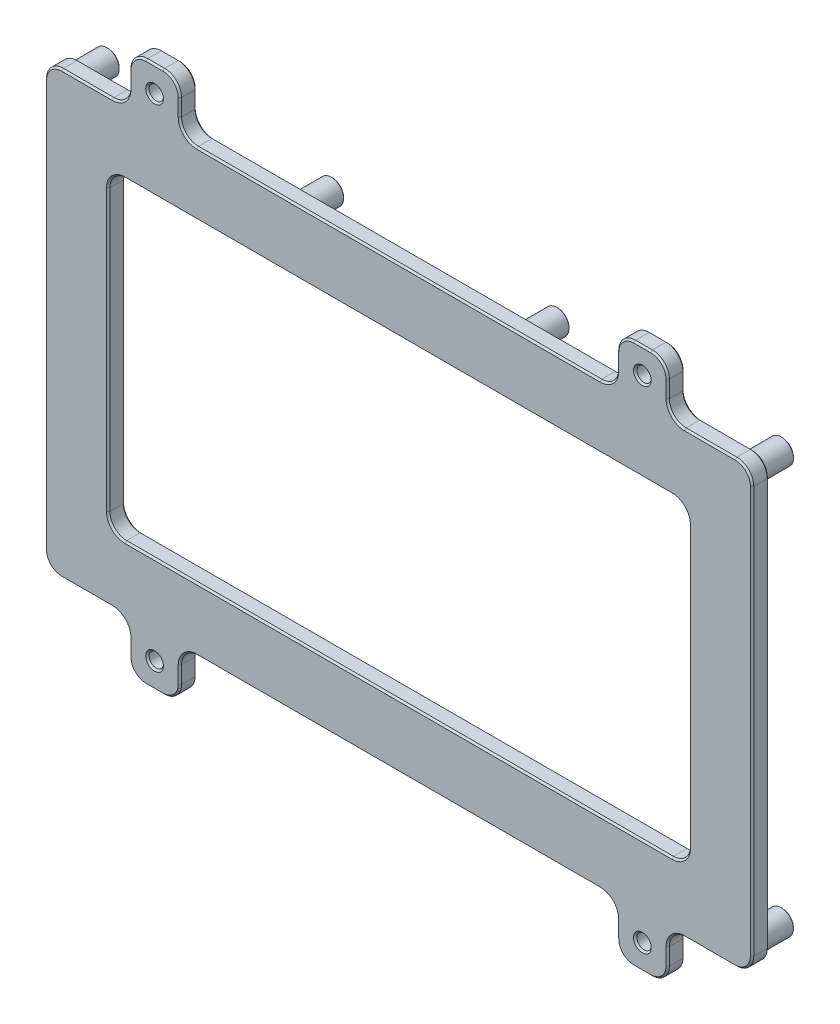
SolidWorks part; units mm, degrees
note: The reader was unsure of these and kept them because the rebuilt part matched: shared geometry of "Sketch1<5>".
ref_plane "Front Plane" through (0, 0, 0) normal (0, 0, 1) x (1, 0, 0)
ref_plane "Top Plane" through (0, 0, 0) normal (0, 1, 0) x (1, 0, 0)
ref_plane "Right Plane" through (0, 0, 0) normal (1, 0, 0) x (0, 0, -1)
sketch "Sketch1" plane through (0, 0, 0) normal (0, 0, 1) x (1, 0, 0)
  line L0 (71.9383, -41.7764) -> (71.9383, -44.6889) construction
  line L1 (-91.7492, -45.6889) -> (75.8508, -45.6889)
  line L2 (-91.7492, -45.6889) -> (-91.7492, 58.7361)
  line L3 (-91.7492, 58.7361) -> (75.8508, 58.7361)
  line L4 (75.8508, -45.6889) -> (75.8508, 58.7361)
  line L5 (71.9383, -41.7764) -> (74.8508, -41.7764) construction
  line L6 (71.9383, 54.8236) -> (71.9383, 57.7361) construction
  line L7 (-87.8367, 54.8236) -> (-90.7492, 54.8236) construction
  line L8 (-7.9492, 58.7361) -> (-7.9492, -45.6889) construction
  line L9 (-91.7492, 6.5236) -> (75.8508, 6.5236) construction
  line L10 (43.8508, 70.7361) -> (55.8508, 58.7361) construction
  line L11 (43.8508, 58.7361) -> (55.8508, 58.7361)
  line L12 (43.8508, 58.7361) -> (43.8508, 70.7361)
  line L13 (43.8508, 70.7361) -> (55.8508, 70.7361)
  line L14 (55.8508, 58.7361) -> (55.8508, 70.7361)
  line L16 (60.8508, -30.6889) -> (-76.7492, -30.6889)
  line L17 (60.8508, -30.6889) -> (60.8508, 43.7361)
  line L18 (60.8508, 43.7361) -> (-76.7492, 43.7361)
  line L19 (-76.7492, -30.6889) -> (-76.7492, 43.7361)
  circle A0 centre (18.7633, -41.7764) radius 0.9125 construction
  circle A1 centre (71.9383, -41.7764) radius 0.9125 construction
  circle A2 centre (71.9383, 54.8236) radius 0.9125 construction
  circle A3 centre (18.7633, 54.8236) radius 0.9125 construction
  circle A4 centre (-34.6617, 54.8236) radius 0.9125 construction
  circle A5 centre (-34.6617, -41.7764) radius 0.9125 construction
  circle A6 centre (-87.8367, -41.7764) radius 0.9125 construction
  circle A7 centre (-87.8367, 54.8236) radius 0.9125 construction
  circle A8 centre (18.7633, -41.7764) radius 0.9125
  circle A9 centre (71.9383, -41.7764) radius 0.9125
  circle A10 centre (71.9383, 54.8236) radius 0.9125
  circle A11 centre (18.7633, 54.8236) radius 0.9125
  circle A12 centre (-34.6617, 54.8236) radius 0.9125
  circle A13 centre (-34.6617, -41.7764) radius 0.9125
  circle A14 centre (-87.8367, -41.7764) radius 0.9125
  circle A15 centre (-87.8367, 54.8236) radius 0.9125
  circle A16 centre (71.9383, 54.8236) radius 2.9125
  circle A17 centre (18.7633, 54.8236) radius 2.9125
  circle A18 centre (-34.6617, 54.8236) radius 2.9125
  circle A19 centre (-87.8367, 54.8236) radius 2.9125
  circle A20 centre (-87.8367, -41.7764) radius 2.9125
  circle A21 centre (-34.6617, -41.7764) radius 2.9125
  circle A22 centre (18.7633, -41.7764) radius 2.9125
  circle A23 centre (71.9383, -41.7764) radius 2.9125
  circle A24 centre (49.8508, 64.7361) radius 1.7
  dimension "D1" = 2
  dimension "D7" = 3.4
  dimension "D2" = 1
  dimension "D3" = 1
  dimension "D4" = 1
  dimension "D5" = 1
  dimension "D6" = 20
  dimension "D8" = 6
  dimension "D9" = 6
  dimension "D10" = 15
  dimension "D11" = 15
  dimension "D12" = 15
  dimension "D13" = 15
extrude "Boss-Extrude1" add sketch "Sketch1" along normal blind 4 contours L3 L4 L1 L2 | L16 L19 L18 L17
sketch "Sketch2" plane through (0, 0, 0) normal (0, 0, -1) x (-1, 0, 0)
  circle A0 centre (87.8367, -41.7764) radius 2.9125 construction
  circle A1 centre (87.8367, -41.7764) radius 0.9125 construction
  circle A2 centre (34.6617, -41.7764) radius 2.9125 construction
  circle A3 centre (34.6617, -41.7764) radius 0.9125 construction
  circle A4 centre (-18.7633, -41.7764) radius 2.9125 construction
  circle A5 centre (-18.7633, -41.7764) radius 0.9125 construction
  circle A6 centre (-71.9383, -41.7764) radius 2.9125 construction
  circle A7 centre (-71.9383, -41.7764) radius 0.9125 construction
  circle A8 centre (-71.9383, 54.8236) radius 0.9125 construction
  circle A9 centre (-71.9383, 54.8236) radius 2.9125 construction
  circle A10 centre (-18.7633, 54.8236) radius 0.9125 construction
  circle A11 centre (-18.7633, 54.8236) radius 2.9125 construction
  circle A12 centre (34.6617, 54.8236) radius 0.9125 construction
  circle A13 centre (34.6617, 54.8236) radius 2.9125 construction
  circle A14 centre (87.8367, 54.8236) radius 0.9125 construction
  circle A15 centre (87.8367, 54.8236) radius 2.9125 construction
  circle A16 centre (87.8367, -41.7764) radius 2.9125
  circle A17 centre (87.8367, -41.7764) radius 0.9125
  circle A18 centre (34.6617, -41.7764) radius 2.9125
  circle A19 centre (34.6617, -41.7764) radius 0.9125
  circle A20 centre (-18.7633, -41.7764) radius 2.9125
  circle A21 centre (-18.7633, -41.7764) radius 0.9125
  circle A22 centre (-71.9383, -41.7764) radius 2.9125
  circle A23 centre (-71.9383, -41.7764) radius 0.9125
  circle A24 centre (-71.9383, 54.8236) radius 0.9125
  circle A25 centre (-71.9383, 54.8236) radius 2.9125
  circle A26 centre (-18.7633, 54.8236) radius 0.9125
  circle A27 centre (-18.7633, 54.8236) radius 2.9125
  circle A28 centre (34.6617, 54.8236) radius 0.9125
  circle A29 centre (34.6617, 54.8236) radius 2.9125
  circle A30 centre (87.8367, 54.8236) radius 0.9125
  circle A31 centre (87.8367, 54.8236) radius 2.9125
extrude "Boss-Extrude2" add sketch "Sketch2" along normal up to surface (7 mm away)
extrude "Boss-Extrude3" add sketch "Sketch1<5>" along normal up to surface (4 mm away) contours L12 L13 L14 L11 | A24 up to face at (-7.9492, 6.5236, 4)
sketch "Sketch1<5>" plane through (0, 0, 0) normal (0, 0, 1) x (1, 0, 0) same geometry as "Sketch1"
ref_plane "Plane1" through (-7.9492, 0, 0) normal (1, 0, 0) x (0, 0, -1)
ref_plane "Plane2" through (0, 6.5236, 0) normal (0, 1, 0) x (1, 0, 0)
mirror "Mirror1" about plane through (-7.9492, 0, 0) normal (1, 0, 0) of "Boss-Extrude3"
mirror "Mirror2" about plane through (0, 6.5236, 0) normal (0, 1, 0) of "Mirror1", "Boss-Extrude3"
fillet "Fillet1" radius 4 24 edges at (-59.7492, 70.7361, 2) (-59.7492, 58.7361, 2) (-71.7492, 70.7361, 2) (-71.7492, 58.7361, 2) (-91.7492, 58.7361, 2) (-91.7492, -45.6889, 2) (-71.7492, -45.6889, 2) (-71.7492, -57.6889, 2) (-59.7492, -57.6889, 2) (-59.7492, -45.6889, 2) (43.8508, -57.6889, 2) (43.8508, -45.6889, 2) (55.8508, -57.6889, 2) (55.8508, -45.6889, 2) (75.8508, -45.6889, 2) (75.8508, 58.7361, 2) (43.8508, 58.7361, 2) (43.8508, 70.7361, 2) (55.8508, 58.7361, 2) (55.8508, 70.7361, 2) (60.8508, -30.6889, 2) (60.8508, 43.7361, 2) (-76.7492, 43.7361, 2) (-76.7492, -30.6889, 2)
chamfer "Chamfer1" distance 0.4 angle 45 112 edges at (48.1508, -51.6889, 4) (-67.4492, -51.6889, 4) (-67.4492, -51.6889, 0) (-67.4492, 64.7361, 4) (48.1508, 64.7361, 4) (51.5508, 64.7361, 0) (-58.5776, 59.9077, 4) (-7.9492, 58.7361, 4) (42.6792, 59.9077, 4) (43.8508, 64.7361, 0) (43.8508, 64.7361, 4) (45.0224, 69.5645, 4) (49.8508, 70.7361, 0) (49.8508, 70.7361, 4) (54.6792, 69.5645, 4) (55.8508, 64.7361, 4) (55.8508, 64.7361, 0) (57.0224, 59.9077, 4) (65.8508, 58.7361, 4) (74.6792, 57.5645, 4) (75.8508, 6.5236, 4) (74.6792, -44.5173, 4) (65.8508, -45.6889, 4) (57.0224, -46.8605, 4) (55.8508, -51.6889, 4) (55.8508, -51.6889, 0) (54.6792, -56.5173, 4) (49.8508, -57.6889, 4) (49.8508, -57.6889, 0) (45.0224, -56.5173, 4) (43.8508, -51.6889, 0) (43.8508, -51.6889, 4) (42.6792, -46.8605, 4) (-7.9492, -45.6889, 4) (-58.5776, -46.8605, 4) (-59.7492, -51.6889, 4) (-59.7492, -51.6889, 0) (-60.9208, -56.5173, 4) (-65.7492, -57.6889, 4) (-65.7492, -57.6889, 0) (-70.5776, -56.5173, 4) (-71.7492, -51.6889, 4) (-71.7492, -51.6889, 0) (-72.9208, -46.8605, 4) (-81.7492, -45.6889, 4) (-90.5776, -44.5173, 4) (-91.7492, 6.5236, 4) (-90.5776, 57.5645, 4) (-81.7492, 58.7361, 4) (-72.9208, 59.9077, 4) (-71.7492, 64.7361, 4) (-71.7492, 64.7361, 0) (-70.5776, 69.5645, 4) (-65.7492, 70.7361, 4) (-65.7492, 70.7361, 0) (-60.9208, 69.5645, 4) (-59.7492, 64.7361, 0) (-59.7492, 64.7361, 4) (51.5508, -51.6889, 0) (-67.4492, 64.7361, 0) (-70.5776, 69.5645, 0) (-72.9208, 59.9077, 0) (-81.7492, 58.7361, 0) (-90.5776, 57.5645, 0) (-91.7492, 6.5236, 0) (-90.5776, -44.5173, 0) (-81.7492, -45.6889, 0) (-72.9208, -46.8605, 0) (-70.5776, -56.5173, 0) (-60.9208, -56.5173, 0) (-58.5776, -46.8605, 0) (-7.9492, -45.6889, 0) (42.6792, -46.8605, 0) (45.0224, -56.5173, 0) (54.6792, -56.5173, 0) (57.0224, -46.8605, 0) (65.8508, -45.6889, 0) (74.6792, -44.5173, 0) (75.8508, 6.5236, 0) (74.6792, 57.5645, 0) (65.8508, 58.7361, 0) (57.0224, 59.9077, 0) (54.6792, 69.5645, 0) (45.0224, 69.5645, 0) (42.6792, 59.9077, 0) (-7.9492, 58.7361, 0) (-58.5776, 59.9077, 0) (-60.9208, 69.5645, 0) (-90.7492, -41.7764, 0) (-37.5742, -41.7764, 0) (15.8508, -41.7764, 0) (69.0258, -41.7764, 0) (69.0258, 54.8236, 0) (15.8508, 54.8236, 0) (-37.5742, 54.8236, 0) (-90.7492, 54.8236, 0) (-7.9492, 43.7361, 4) (-76.7492, 6.5236, 4) (-7.9492, -30.6889, 4) (60.8508, 6.5236, 4) (-76.7492, 6.5236, 0) (-7.9492, 43.7361, 0) (60.8508, 6.5236, 0) (-7.9492, -30.6889, 0) (59.6792, 42.5645, 4) (-75.5776, 42.5645, 4) (-75.5776, -29.5173, 4) (59.6792, -29.5173, 4) (-75.5776, -29.5173, 0) (-75.5776, 42.5645, 0) (59.6792, 42.5645, 0) (59.6792, -29.5173, 0)
chamfer "Chamfer2" distance 0.2 angle 45 16 edges at (74.8508, 54.8236, -7) (72.8508, 54.8236, -7) (21.6758, 54.8236, -7) (19.6758, 54.8236, -7) (-31.7492, 54.8236, -7) (-33.7492, 54.8236, -7) (-84.9242, 54.8236, -7) (-86.9242, 54.8236, -7) (-31.7492, -41.7764, -7) (-33.7492, -41.7764, -7) (-84.9242, -41.7764, -7) (-86.9242, -41.7764, -7) (21.6758, -41.7764, -7) (19.6758, -41.7764, -7) (74.8508, -41.7764, -7) (72.8508, -41.7764, -7)
